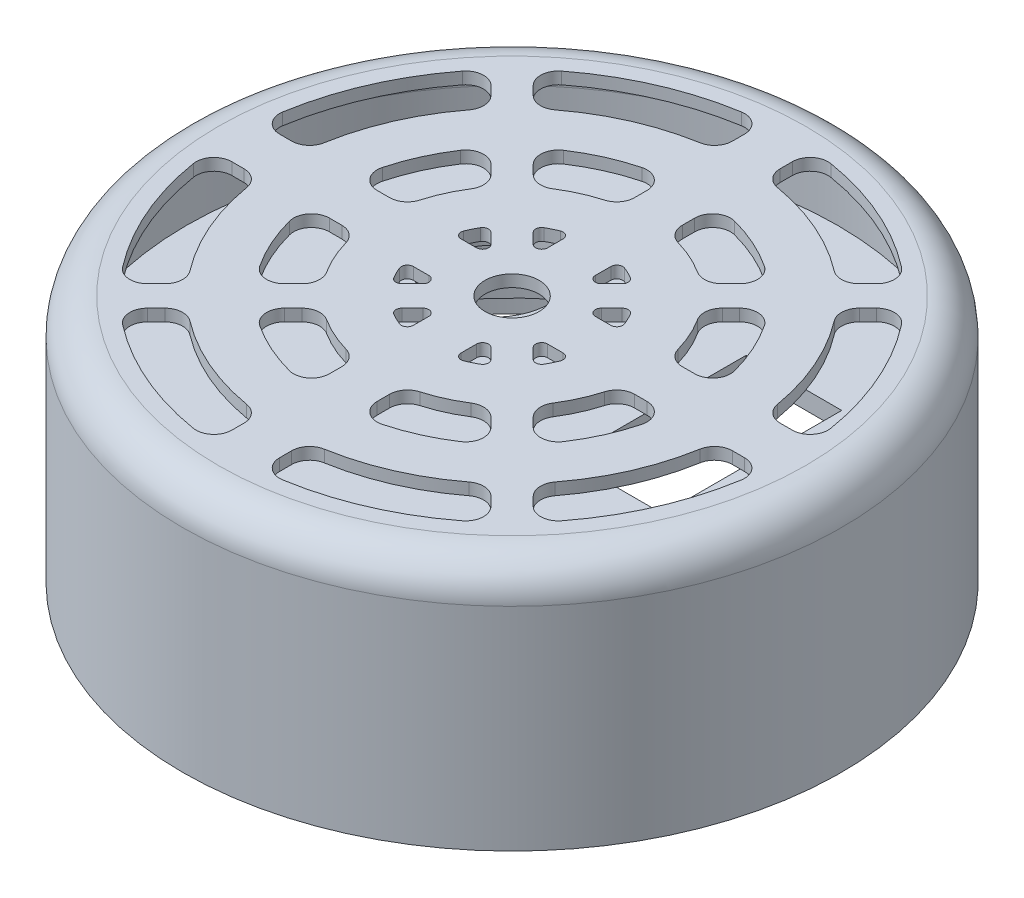
SolidWorks part; units mm, degrees
ref_plane "Front Plane" through (0, 0, 0) normal (0, 0, 1) x (1, 0, 0)
ref_plane "Top Plane" through (0, 0, 0) normal (0, 1, 0) x (1, 0, 0)
ref_plane "Right Plane" through (0, 0, 0) normal (1, 0, 0) x (0, 0, -1)
sketch "Sketch1" plane through (0, 0, 0) normal (0, 1, 0) x (1, 0, 0)
  circle A1 centre (0, 0) radius 55.2
  dimension "D2" = 110.4
extrude "Boss-Extrude1" add sketch "Sketch1" along normal blind 3
sketch "Sketch2" plane through (0, 3, 0) normal (0, 1, 0) x (1, 0, 0)
  circle A0 centre (0, 0) radius 55
  dimension "D1" = 110
extrude "Cut-Extrude1" cut sketch "Sketch2" against normal through all
sketch "Sketch4" plane through (0, 3, 0) normal (0, 1, 0) x (1, 0, 0)
  line L0 (0, 0) -> (8.2385, 0) construction
  line L1 (8.2385, 0) -> (0, 0) construction
  line L2 (0, 0) -> (0, 11.6273) construction
  line L3 (-45.2, -5) -> (-45.2, 5)
  line L4 (-45.2, -5) -> (-53.768, -5)
  line L5 (-45.2, 5) -> (-53.768, 5)
  circle A1 centre (0, 0) radius 55.2
  circle A2 centre (0, 0) radius 55.2
  arc A3 (-53.768, -5) -> (-53.768, 5) centre (0, 0) ccw
  point P12 (-45.2, 0)
  dimension "D2" = 110.4
  dimension "D3" = 108
  dimension "D4" = 10
  dimension "D5" = 10
  dimension "D1" = 0
extrude "Boss-Extrude2" add sketch "Sketch4" along normal blind 18.5
sketch "Sketch8" plane through (0, 3, 0) normal (0, -1, 0) x (1, 0, 0)
  line L2 (-53.768, -5) -> (-45.2, -5) construction
  line L3 (-45.2, 5) -> (-54.7723, 5)
  line L4 (-45.2, 5) -> (-45.2, -5)
  line L5 (-45.2, -5) -> (-54.7723, -5)
  circle A2 centre (0, 0) radius 55 construction
  arc A3 (-54.7723, 5) -> (-54.7723, -5) centre (0, 0) ccw
extrude "Boss-Extrude4" add sketch "Sketch8" along normal blind 3
sketch "Sketch6" plane through (0, 21.5, 0) normal (0, 1, 0) x (1, 0, 0)
  line L1 (11.2131, 28) -> (27.2131, 28)
  line L2 (11.2131, 28) -> (11.2131, -2)
  line L3 (11.2131, -2) -> (27.2131, -2)
  line L4 (27.2131, 28) -> (27.2131, -2)
  line L5 (11.2131, 28) -> (27.2131, -2) construction
  line L6 (11.2131, -2) -> (27.2131, 28) construction
  line L7 (12.1174, 28) -> (26.3174, 28) construction
  circle A0 centre (0, 0) radius 55.2
  circle A1 centre (-22.2011, 19.0599) radius 9.5
  point P5 (19.2131, 13)
  dimension "D1" = 19
  dimension "D2" = 30
  dimension "D3" = 16
  dimension "D6" = 110.4
  dimension "D4" = 19.2131
  dimension "D5" = 13
  dimension "D7" = 19.0599
  dimension "D8" = 22.2011
extrude "Boss-Extrude3" add sketch "Sketch6" along normal blind 3
sketch "Sketch9" plane through (0, 24.5, 0) normal (0, 1, 0) x (1, 0, 0)
  circle A0 centre (0, 0) radius 55.2
  circle A1 centre (0, 0) radius 54.5
  dimension "D1" = 110.4
  dimension "D2" = 109
extrude "Boss-Extrude5" add sketch "Sketch9" along normal blind 15
sketch "Sketch10" plane through (0, 39.5, 0) normal (0, 1, 0) x (1, 0, 0)
  line L0 (0, 0) -> (18.0348, 0) construction
  line L2 (0, 0) -> (0, 14.913) construction
  line L5 (0, 0) -> (-39.0323, 39.0323) construction
  line L10 (-4, 40.9054) -> (-4, 42.9331)
  line L11 (-4, 24.5204) -> (-4, 26.5942)
  line L12 (-4, 9.9497) -> (-4, 12.5399)
  line L14 (-12.5399, 4) -> (-9.9497, 4)
  line L15 (-26.5942, 4) -> (-24.5204, 4)
  line L16 (-42.9331, 4) -> (-40.9054, 4)
  line L21 (-27.3183, 30.8538) -> (-28.7445, 32.2801)
  line L22 (-30.8538, 27.3183) -> (-32.2801, 28.7445)
  line L23 (-15.839, 19.3746) -> (-17.2848, 20.8203)
  line L24 (-19.3746, 15.839) -> (-20.8203, 17.2848)
  line L25 (-5.7071, 9.2426) -> (-7.4518, 10.9873)
  line L26 (-9.2426, 5.7071) -> (-10.9873, 7.4518)
  line L51 (9.2426, 5.7071) -> (10.9873, 7.4518)
  line L52 (12.5399, 4) -> (9.9497, 4)
  line L53 (5.7071, 9.2426) -> (7.4518, 10.9873)
  line L54 (4, 9.9497) -> (4, 12.5399)
  line L55 (4, 24.5204) -> (4, 26.5942)
  line L56 (15.839, 19.3746) -> (17.2848, 20.8203)
  line L57 (19.3746, 15.839) -> (20.8203, 17.2848)
  line L58 (26.5942, 4) -> (24.5204, 4)
  line L59 (42.9331, 4) -> (40.9054, 4)
  line L60 (30.8538, 27.3183) -> (32.2801, 28.7445)
  line L61 (4, 40.9054) -> (4, 42.9331)
  line L62 (27.3183, 30.8538) -> (28.7445, 32.2801)
  line L63 (30.8538, -27.3183) -> (32.2801, -28.7445)
  line L64 (42.9331, -4) -> (40.9054, -4)
  line L65 (26.5942, -4) -> (24.5204, -4)
  line L66 (19.3746, -15.839) -> (20.8203, -17.2848)
  line L67 (9.2426, -5.7071) -> (10.9873, -7.4518)
  line L68 (12.5399, -4) -> (9.9497, -4)
  line L69 (-9.2426, -5.7071) -> (-10.9873, -7.4518)
  line L70 (-12.5399, -4) -> (-9.9497, -4)
  line L71 (-5.7071, -9.2426) -> (-7.4518, -10.9873)
  line L72 (-4, -9.9497) -> (-4, -12.5399)
  line L73 (4, -9.9497) -> (4, -12.5399)
  line L74 (5.7071, -9.2426) -> (7.4518, -10.9873)
  line L75 (4, -24.5204) -> (4, -26.5942)
  line L76 (15.839, -19.3746) -> (17.2848, -20.8203)
  line L77 (4, -40.9054) -> (4, -42.9331)
  line L78 (27.3183, -30.8538) -> (28.7445, -32.2801)
  line L79 (-4, -24.5204) -> (-4, -26.5942)
  line L80 (-15.839, -19.3746) -> (-17.2848, -20.8203)
  line L81 (-19.3746, -15.839) -> (-20.8203, -17.2848)
  line L82 (-26.5942, -4) -> (-24.5204, -4)
  line L83 (-42.9331, -4) -> (-40.9054, -4)
  line L84 (-30.8538, -27.3183) -> (-32.2801, -28.7445)
  line L85 (-4, -40.9054) -> (-4, -42.9331)
  line L86 (-27.3183, -30.8538) -> (-28.7445, -32.2801)
  circle A0 centre (0, 0) radius 55.2
  arc A1 (-36.7739, 28.4593) -> (-45.894, 7.4828) centre (0, 0) ccw
  circle A2 centre (0, 0) radius 54.5 construction
  arc A3 (-30.5914, 23.3755) -> (-37.9484, 6.494) centre (0, 0) ccw
  circle A7 centre (0, 0) radius 4.5314
  arc A10 (-25.4444, 16.8177) -> (-29.4954, 7.7636) centre (0, 0) ccw
  arc A11 (-18.967, 12.1039) -> (-21.6356, 6.1765) centre (0, 0) ccw
  arc A12 (-7.4828, 45.894) -> (-28.4593, 36.7739) centre (0, 0) ccw
  arc A13 (-6.494, 37.9484) -> (-23.3755, 30.5914) centre (0, 0) ccw
  arc A14 (-7.7636, 29.4954) -> (-16.8177, 25.4444) centre (0, 0) ccw
  arc A15 (-6.1765, 21.6356) -> (-12.1039, 18.967) centre (0, 0) ccw
  arc A16 (-5.3704, 13.4688) -> (-7.2443, 12.5607) centre (0, 0) ccw
  arc A17 (-12.5607, 7.2443) -> (-13.4688, 5.3704) centre (0, 0) ccw
  arc A46 (-4, 24.5204) -> (-6.1765, 21.6356) centre (-7, 24.5204) cw
  arc A47 (-15.839, 19.3746) -> (-12.1039, 18.967) centre (-13.7177, 21.4959) ccw
  arc A48 (-16.8177, 25.4444) -> (-17.2848, 20.8203) centre (-15.1635, 22.9416) ccw
  arc A49 (-7.7636, 29.4954) -> (-4, 26.5942) centre (-7, 26.5942) cw
  arc A50 (-4, 40.9054) -> (-6.494, 37.9484) centre (-7, 40.9054) cw
  arc A51 (-7.4828, 45.894) -> (-4, 42.9331) centre (-7, 42.9331) cw
  arc A52 (-28.4593, 36.7739) -> (-28.7445, 32.2801) centre (-26.6232, 34.4014) ccw
  arc A53 (-27.3183, 30.8538) -> (-23.3755, 30.5914) centre (-25.197, 32.9752) ccw
  arc A54 (-25.4444, 16.8177) -> (-20.8203, 17.2848) centre (-22.9416, 15.1635) cw
  arc A55 (-19.3746, 15.839) -> (-18.967, 12.1039) centre (-21.4959, 13.7177) cw
  arc A56 (-21.6356, 6.1765) -> (-24.5204, 4) centre (-24.5204, 7) cw
  arc A57 (-26.5942, 4) -> (-29.4954, 7.7636) centre (-26.5942, 7) cw
  arc A58 (-37.9484, 6.494) -> (-40.9054, 4) centre (-40.9054, 7) cw
  arc A59 (-30.8538, 27.3183) -> (-30.5914, 23.3755) centre (-32.9752, 25.197) cw
  arc A60 (-42.9331, 4) -> (-45.894, 7.4828) centre (-42.9331, 7) cw
  arc A61 (-36.7739, 28.4593) -> (-32.2801, 28.7445) centre (-34.4014, 26.6232) cw
  arc A62 (-5.7071, 9.2426) -> (-4, 9.9497) centre (-5, 9.9497) ccw
  arc A63 (-9.2426, 5.7071) -> (-9.9497, 4) centre (-9.9497, 5) cw
  arc A64 (-12.5607, 7.2443) -> (-10.9873, 7.4518) centre (-11.6944, 6.7447) cw
  arc A65 (-12.5399, 4) -> (-13.4688, 5.3704) centre (-12.5399, 5) cw
  arc A66 (-7.2443, 12.5607) -> (-7.4518, 10.9873) centre (-6.7447, 11.6944) ccw
  arc A67 (-5.3704, 13.4688) -> (-4, 12.5399) centre (-5, 12.5399) cw
  arc A68 (12.5607, 7.2443) -> (13.4688, 5.3704) centre (0, 0) cw
  arc A69 (12.5607, 7.2443) -> (10.9873, 7.4518) centre (11.6944, 6.7447) ccw
  arc A70 (9.2426, 5.7071) -> (9.9497, 4) centre (9.9497, 5) ccw
  arc A71 (12.5399, 4) -> (13.4688, 5.3704) centre (12.5399, 5) ccw
  arc A72 (7.2443, 12.5607) -> (7.4518, 10.9873) centre (6.7447, 11.6944) cw
  arc A73 (5.3704, 13.4688) -> (7.2443, 12.5607) centre (0, 0) cw
  arc A74 (5.7071, 9.2426) -> (4, 9.9497) centre (5, 9.9497) cw
  arc A75 (5.3704, 13.4688) -> (4, 12.5399) centre (5, 12.5399) ccw
  arc A76 (6.1765, 21.6356) -> (12.1039, 18.967) centre (0, 0) cw
  arc A77 (4, 24.5204) -> (6.1765, 21.6356) centre (7, 24.5204) ccw
  arc A78 (7.7636, 29.4954) -> (4, 26.5942) centre (7, 26.5942) ccw
  arc A79 (7.7636, 29.4954) -> (16.8177, 25.4444) centre (0, 0) cw
  arc A80 (15.839, 19.3746) -> (12.1039, 18.967) centre (13.7177, 21.4959) cw
  arc A81 (16.8177, 25.4444) -> (17.2848, 20.8203) centre (15.1635, 22.9416) cw
  arc A82 (25.4444, 16.8177) -> (20.8203, 17.2848) centre (22.9416, 15.1635) ccw
  arc A83 (25.4444, 16.8177) -> (29.4954, 7.7636) centre (0, 0) cw
  arc A84 (26.5942, 4) -> (29.4954, 7.7636) centre (26.5942, 7) ccw
  arc A85 (19.3746, 15.839) -> (18.967, 12.1039) centre (21.4959, 13.7177) ccw
  arc A86 (21.6356, 6.1765) -> (24.5204, 4) centre (24.5204, 7) ccw
  arc A87 (18.967, 12.1039) -> (21.6356, 6.1765) centre (0, 0) cw
  arc A88 (30.5914, 23.3755) -> (37.9484, 6.494) centre (0, 0) cw
  arc A89 (37.9484, 6.494) -> (40.9054, 4) centre (40.9054, 7) ccw
  arc A90 (42.9331, 4) -> (45.894, 7.4828) centre (42.9331, 7) ccw
  arc A91 (36.7739, 28.4593) -> (45.894, 7.4828) centre (0, 0) cw
  arc A92 (30.8538, 27.3183) -> (30.5914, 23.3755) centre (32.9752, 25.197) ccw
  arc A93 (36.7739, 28.4593) -> (32.2801, 28.7445) centre (34.4014, 26.6232) ccw
  arc A94 (6.494, 37.9484) -> (23.3755, 30.5914) centre (0, 0) cw
  arc A95 (4, 40.9054) -> (6.494, 37.9484) centre (7, 40.9054) ccw
  arc A96 (7.4828, 45.894) -> (4, 42.9331) centre (7, 42.9331) ccw
  arc A97 (7.4828, 45.894) -> (28.4593, 36.7739) centre (0, 0) cw
  arc A98 (28.4593, 36.7739) -> (28.7445, 32.2801) centre (26.6232, 34.4014) cw
  arc A99 (27.3183, 30.8538) -> (23.3755, 30.5914) centre (25.197, 32.9752) cw
  arc A100 (30.8538, -27.3183) -> (30.5914, -23.3755) centre (32.9752, -25.197) cw
  arc A101 (36.7739, -28.4593) -> (32.2801, -28.7445) centre (34.4014, -26.6232) cw
  arc A102 (36.7739, -28.4593) -> (45.894, -7.4828) centre (0, 0) ccw
  arc A103 (42.9331, -4) -> (45.894, -7.4828) centre (42.9331, -7) cw
  arc A104 (37.9484, -6.494) -> (40.9054, -4) centre (40.9054, -7) cw
  arc A105 (30.5914, -23.3755) -> (37.9484, -6.494) centre (0, 0) ccw
  arc A106 (19.3746, -15.839) -> (18.967, -12.1039) centre (21.4959, -13.7177) cw
  arc A107 (18.967, -12.1039) -> (21.6356, -6.1765) centre (0, 0) ccw
  arc A108 (21.6356, -6.1765) -> (24.5204, -4) centre (24.5204, -7) cw
  arc A109 (26.5942, -4) -> (29.4954, -7.7636) centre (26.5942, -7) cw
  arc A110 (25.4444, -16.8177) -> (29.4954, -7.7636) centre (0, 0) ccw
  arc A111 (25.4444, -16.8177) -> (20.8203, -17.2848) centre (22.9416, -15.1635) cw
  arc A112 (12.5607, -7.2443) -> (10.9873, -7.4518) centre (11.6944, -6.7447) cw
  arc A113 (9.2426, -5.7071) -> (9.9497, -4) centre (9.9497, -5) cw
  arc A114 (12.5399, -4) -> (13.4688, -5.3704) centre (12.5399, -5) cw
  arc A115 (12.5607, -7.2443) -> (13.4688, -5.3704) centre (0, 0) ccw
  arc A116 (-12.5607, -7.2443) -> (-13.4688, -5.3704) centre (0, 0) cw
  arc A117 (-12.5607, -7.2443) -> (-10.9873, -7.4518) centre (-11.6944, -6.7447) ccw
  arc A118 (-9.2426, -5.7071) -> (-9.9497, -4) centre (-9.9497, -5) ccw
  arc A119 (-12.5399, -4) -> (-13.4688, -5.3704) centre (-12.5399, -5) ccw
  arc A120 (-7.2443, -12.5607) -> (-7.4518, -10.9873) centre (-6.7447, -11.6944) cw
  arc A121 (-5.3704, -13.4688) -> (-7.2443, -12.5607) centre (0, 0) cw
  arc A122 (-5.7071, -9.2426) -> (-4, -9.9497) centre (-5, -9.9497) cw
  arc A123 (-5.3704, -13.4688) -> (-4, -12.5399) centre (-5, -12.5399) ccw
  arc A124 (5.7071, -9.2426) -> (4, -9.9497) centre (5, -9.9497) ccw
  arc A125 (5.3704, -13.4688) -> (4, -12.5399) centre (5, -12.5399) cw
  arc A126 (5.3704, -13.4688) -> (7.2443, -12.5607) centre (0, 0) ccw
  arc A127 (7.2443, -12.5607) -> (7.4518, -10.9873) centre (6.7447, -11.6944) ccw
  arc A128 (4, -24.5204) -> (6.1765, -21.6356) centre (7, -24.5204) cw
  arc A129 (7.7636, -29.4954) -> (4, -26.5942) centre (7, -26.5942) cw
  arc A130 (7.7636, -29.4954) -> (16.8177, -25.4444) centre (0, 0) ccw
  arc A131 (16.8177, -25.4444) -> (17.2848, -20.8203) centre (15.1635, -22.9416) ccw
  arc A132 (15.839, -19.3746) -> (12.1039, -18.967) centre (13.7177, -21.4959) ccw
  arc A133 (6.1765, -21.6356) -> (12.1039, -18.967) centre (0, 0) ccw
  arc A134 (4, -40.9054) -> (6.494, -37.9484) centre (7, -40.9054) cw
  arc A135 (7.4828, -45.894) -> (4, -42.9331) centre (7, -42.9331) cw
  arc A136 (7.4828, -45.894) -> (28.4593, -36.7739) centre (0, 0) ccw
  arc A137 (28.4593, -36.7739) -> (28.7445, -32.2801) centre (26.6232, -34.4014) ccw
  arc A138 (27.3183, -30.8538) -> (23.3755, -30.5914) centre (25.197, -32.9752) ccw
  arc A139 (6.494, -37.9484) -> (23.3755, -30.5914) centre (0, 0) ccw
  arc A140 (-6.1765, -21.6356) -> (-12.1039, -18.967) centre (0, 0) cw
  arc A141 (-4, -24.5204) -> (-6.1765, -21.6356) centre (-7, -24.5204) ccw
  arc A142 (-7.7636, -29.4954) -> (-4, -26.5942) centre (-7, -26.5942) ccw
  arc A143 (-7.7636, -29.4954) -> (-16.8177, -25.4444) centre (0, 0) cw
  arc A144 (-15.839, -19.3746) -> (-12.1039, -18.967) centre (-13.7177, -21.4959) cw
  arc A145 (-16.8177, -25.4444) -> (-17.2848, -20.8203) centre (-15.1635, -22.9416) cw
  arc A146 (-25.4444, -16.8177) -> (-20.8203, -17.2848) centre (-22.9416, -15.1635) ccw
  arc A147 (-25.4444, -16.8177) -> (-29.4954, -7.7636) centre (0, 0) cw
  arc A148 (-26.5942, -4) -> (-29.4954, -7.7636) centre (-26.5942, -7) ccw
  arc A149 (-19.3746, -15.839) -> (-18.967, -12.1039) centre (-21.4959, -13.7177) ccw
  arc A150 (-21.6356, -6.1765) -> (-24.5204, -4) centre (-24.5204, -7) ccw
  arc A151 (-18.967, -12.1039) -> (-21.6356, -6.1765) centre (0, 0) cw
  arc A152 (-30.5914, -23.3755) -> (-37.9484, -6.494) centre (0, 0) cw
  arc A153 (-37.9484, -6.494) -> (-40.9054, -4) centre (-40.9054, -7) ccw
  arc A154 (-42.9331, -4) -> (-45.894, -7.4828) centre (-42.9331, -7) ccw
  arc A155 (-36.7739, -28.4593) -> (-45.894, -7.4828) centre (0, 0) cw
  arc A156 (-30.8538, -27.3183) -> (-30.5914, -23.3755) centre (-32.9752, -25.197) ccw
  arc A157 (-36.7739, -28.4593) -> (-32.2801, -28.7445) centre (-34.4014, -26.6232) ccw
  arc A158 (-6.494, -37.9484) -> (-23.3755, -30.5914) centre (0, 0) cw
  arc A159 (-4, -40.9054) -> (-6.494, -37.9484) centre (-7, -40.9054) ccw
  arc A160 (-7.4828, -45.894) -> (-4, -42.9331) centre (-7, -42.9331) ccw
  arc A161 (-7.4828, -45.894) -> (-28.4593, -36.7739) centre (0, 0) cw
  arc A162 (-28.4593, -36.7739) -> (-28.7445, -32.2801) centre (-26.6232, -34.4014) cw
  arc A163 (-27.3183, -30.8538) -> (-23.3755, -30.5914) centre (-25.197, -32.9752) cw
  point P18 (0, 0)
  point P24 (-4, 30.2366)
  point P29 (-4, 38.2916)
  point P34 (-4, 46.3276)
  point P73 (-4, 7.5355)
  dimension "D1" = 110.4
  dimension "D2" = 8
  dimension "D3" = 8
  dimension "D4" = 8.0551
  dimension "D5" = 8
  dimension "D6" = 4
  dimension "D7" = 8
  dimension "D9" = 8
  dimension "D11" = 2.5
  dimension "D14" = 4
  dimension "D12" = 5.9686
  dimension "D13" = 3
  dimension "D16" = 1
  dimension "D8" = 45
  dimension "D10" = 2.5
  dimension "D15" = 4
extrude "Boss-Extrude6" add sketch "Sketch10" along normal blind 2
sketch "Sketch15" plane through (0, 3, 0) normal (0, -1, 0) x (1, 0, 0)
  line L0 (0, 0) -> (0, 9.6411) construction
  line L1 (0, 0) -> (7.7973, 0) construction
  circle A1 centre (0, 42) radius 3
  circle A3 centre (0, -37) radius 3
  dimension "D2" = 37
  dimension "D4" = 6
  dimension "D1" = 6
  dimension "D3" = 42
extrude "Boss-Extrude9" add sketch "Sketch15" against normal up to next
hole_wizard "Ø3.0mm Dowel Hole2" positions "3DSketch4" profile "Sketch17" hole size "Ø3.0" standard "DIN"
sketch3d "3DSketch4"
  line L0 (0, 21.5, 42) -> (0, 3, 42) construction
  line L1 (0, 21.5, -37) -> (0, 3, -37) construction
  point P0 (0, 3, 42)
  point P4 (0, 3, -37)
sketch "Sketch17" plane through (0, 3, 42) normal (1, 0, 0) x (0, 0, -1)
  line L0 (0, 0) -> (0, 14.9013)
  line L1 (0, 14.9013) -> (1.5, 14)
  line L2 (1.5, 14) -> (1.5, 0)
  line L5 (1.5, 0) -> (0, 0)
  line L10 (0, 14.9013) -> (-1.5, 14) construction
  line L11 (0, -6.35) -> (0, 107.95) construction
  dimension "Hole Dia." = 3
  dimension "Hole Depth" = 14
  dimension "Drill Angle" = 118
fillet "Fillet3" radius 6 2 edges at (0, 39.5, 54.5) (0, 41.5, 55.2)
